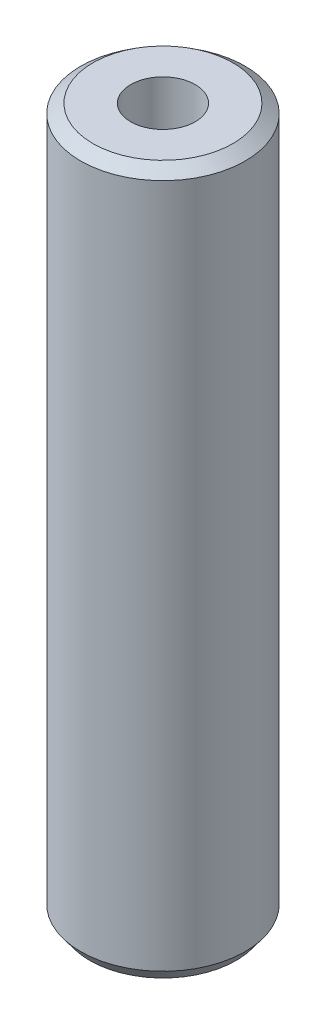
SolidWorks part; units mm, degrees
ref_plane "Front Plane" through (0, 0, 0) normal (0, 0, 1) x (1, 0, 0)
ref_plane "Top Plane" through (0, 0, 0) normal (0, 1, 0) x (1, 0, 0)
ref_plane "Right Plane" through (0, 0, 0) normal (1, 0, 0) x (0, 0, -1)
sketch "Sketch1" plane through (0, 0, 0) normal (0, 1, 0) x (1, 0, 0)
  circle A0 centre (0, 0) radius 30
  dimension "SHAFT_OD" = 60
extrude "Boss-Extrude1" add sketch "Sketch1" along normal blind 257.5523
sketch "Sketch2" plane through (0, 0, 0) normal (0, 1, 0) x (1, 0, 0)
  circle A0 centre (0, 0) radius 11.7693
  dimension "BORE_D" = 23.5387
extrude "Cut-Extrude1" cut sketch "Sketch2" along normal through all
chamfer "Chamfer1" distance 3.2872 angle 53.556 2 edges at (0, 257.5523, 30) (0, 0, 30) first distance on face at (0, 257.5523, 30) first distance on face at (0, 0, 11.7693)
